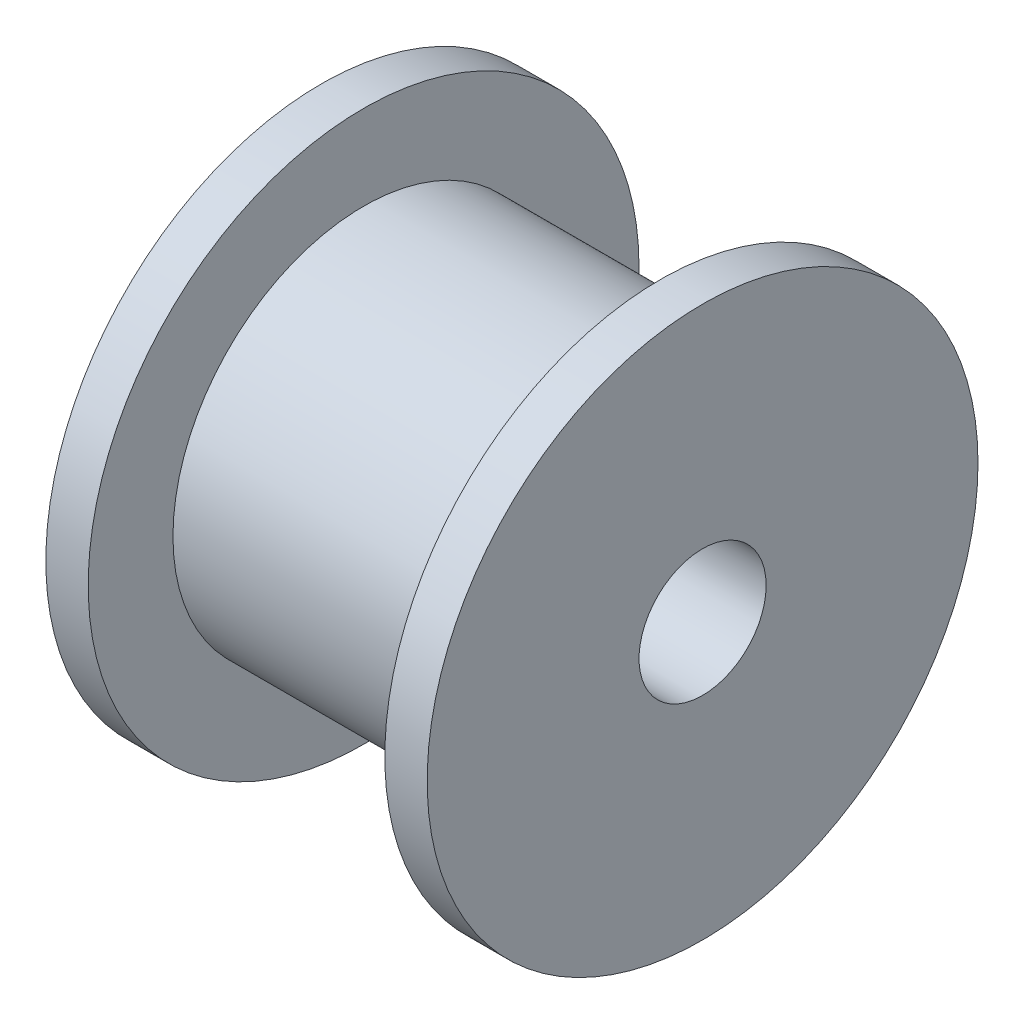
SolidWorks part; units mm, degrees
ref_plane "Front Plane" through (0, 0, 0) normal (0, 0, 1) x (1, 0, 0)
ref_plane "Top Plane" through (0, 0, 0) normal (0, 1, 0) x (1, 0, 0)
ref_plane "Right Plane" through (0, 0, 0) normal (1, 0, 0) x (0, 0, -1)
sketch "Sketch1" plane through (0, 0, 0) normal (1, 0, 0) x (0, 0, -1)
  circle A0 centre (0, 0) radius 6.5
  circle A1 centre (0, 0) radius 4.5
  circle A2 centre (0, 0) radius 1.5
  dimension "D1" = 3
  dimension "D2" = 13
  dimension "D3" = 2
extrude "Boss-Extrude1" add sketch "Sketch1" along normal blind 4.5 and the other way blind 4.5 contours A1 A2 | A0 A1 region at (0, 0, 6.3162) region at (0, 0, 4.3727)
extrude "Cut-Extrude1" cut sketch "Sketch1<3>" against normal blind 3.5 and the other way blind 3.5 contours A0 A1 region at (0, 0, 6.3162)
sketch "Sketch1<3>" plane through (0, 0, 0) normal (1, 0, 0) x (0, 0, -1) same geometry as "Sketch1"
